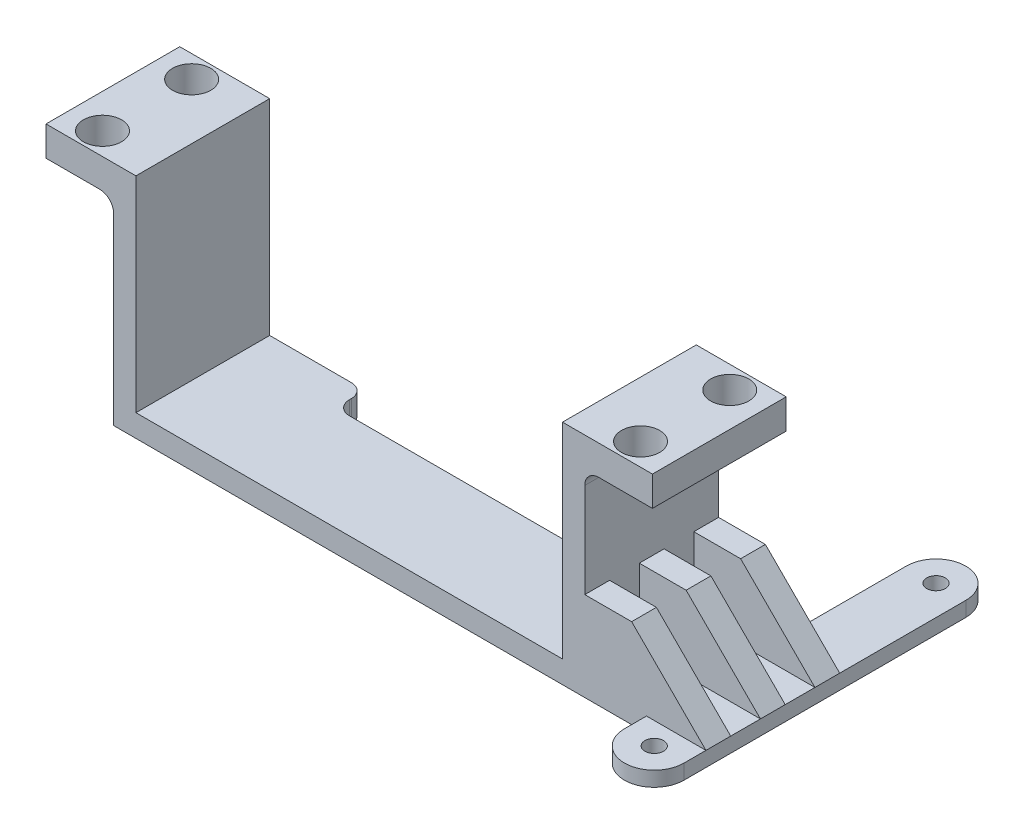
SolidWorks part; units mm, degrees
ref_plane "Front Plane" through (0, 0, 0) normal (0, 0, 1) x (1, 0, 0)
ref_plane "Top Plane" through (0, 0, 0) normal (0, 1, 0) x (1, 0, 0)
ref_plane "Right Plane" through (0, 0, 0) normal (1, 0, 0) x (0, 0, -1)
sketch "Sketch1" plane through (0, 0, 0) normal (0, 0, 1) x (1, 0, 0)
  line L0 (-3.81, 35.052) -> (0, 35.052)
  line L1 (0, 0) -> (72.898, 0)
  line L2 (0, 0) -> (0, 35.052)
  line L4 (72.898, 0) -> (72.898, 35.052)
  line L6 (-3.81, 35.052) -> (-3.81, -3.81)
  line L7 (-3.81, -3.81) -> (76.708, -3.81)
  line L8 (76.708, 35.052) -> (76.708, -3.81)
  line L9 (72.898, 35.052) -> (76.708, 35.052)
  dimension "D1" = 3.81
  dimension "D2" = 3.81
  dimension "D3" = 3.81
  dimension "D4" = 38.862
  dimension "D5" = 72.898
extrude "Boss-Extrude1" add sketch "Sketch1" along normal blind 22.86
sketch "Sketch2" plane through (0, -3.81, 0) normal (0, -1, 0) x (1, 0, 0)
  line L0 (92.329, 26.6192) -> (92.329, -21.5392) construction
  line L2 (87.249, 26.6192) -> (87.249, 22.86)
  line L3 (97.409, 26.6192) -> (97.409, -21.5392)
  line L4 (-3.81, 22.86) -> (76.708, 22.86) construction
  line L5 (76.708, 22.86) -> (76.708, 0) construction
  line L6 (76.708, 22.86) -> (87.249, 22.86)
  line L7 (76.708, 22.86) -> (76.708, 0)
  line L8 (76.708, 0) -> (87.249, 0)
  line L9 (87.249, 0) -> (87.249, -21.5392)
  circle A0 centre (92.329, 26.6192) radius 1.5875
  circle A1 centre (92.329, -21.5392) radius 1.5875
  arc A2 (97.409, 26.6192) -> (87.249, 26.6192) centre (92.329, 26.6192) ccw
  arc A3 (87.249, -21.5392) -> (97.409, -21.5392) centre (92.329, -21.5392) ccw
  point P4 (92.329, 2.54)
  point P5 (76.708, 11.43)
  point P6 (36.449, 22.86)
  point P9 (92.329, 25.0317)
  point P14 (92.329, -19.9517)
  dimension "D2" = 3.175
  dimension "D3" = 5.08
  dimension "D1" = 44.9834
  dimension "D4" = 55.88
  dimension "D5" = 8.89
extrude "Boss-Extrude2" add sketch "Sketch2" against normal blind 2.54
sketch "Sketch4" plane through (0, 35.052, 0) normal (0, 1, 0) x (1, 0, 0)
  line L0 (0, -22.86) -> (-3.81, -22.86) construction
  line L1 (0, 0) -> (-15.367, 0)
  line L2 (0, 0) -> (0, -22.86)
  line L3 (0, -22.86) -> (-15.367, -22.86)
  line L4 (-15.367, 0) -> (-15.367, -22.86)
  line L5 (-3.81, -22.86) -> (-3.81, 0) construction
  line L6 (-9.525, -3.81) -> (-9.525, -19.05) construction
  circle A0 centre (-9.525, -3.81) radius 3.2639
  circle A1 centre (-9.525, -19.05) radius 3.2639
  point P13 (-15.367, -11.43)
  point P14 (-9.525, -11.43)
  dimension "D1" = 6.5278
  dimension "D2" = 5.715
  dimension "D3" = 7.62
  dimension "D4" = 5.842
extrude "Boss-Extrude3" add sketch "Sketch4" against normal blind 5.08
ref_plane "Plane1" through (36.449, 0, 0) normal (1, 0, 0) x (0, 0, -1)
mirror "Mirror1" about plane through (36.449, 0, 0) normal (1, 0, 0) of "Boss-Extrude3"
sketch "Sketch5" plane through (0, -1.27, 0) normal (0, 1, 0) x (1, 0, 0)
  line L0 (97.409, 21.5392) -> (97.409, -26.6192) construction
  line L1 (76.708, 0) -> (97.409, 0)
  line L2 (76.708, 0) -> (76.708, -4.2333)
  line L3 (76.708, -4.2333) -> (97.409, -4.2333)
  line L4 (97.409, 0) -> (97.409, -4.2333)
  line L5 (76.708, -22.86) -> (76.708, 0) construction
  line L6 (76.708, -22.86) -> (97.409, -22.86)
  line L7 (76.708, -22.86) -> (76.708, -18.6267)
  line L8 (76.708, -18.6267) -> (97.409, -18.6267)
  line L9 (97.409, -22.86) -> (97.409, -18.6267)
  line L10 (76.708, -9.3133) -> (97.409, -9.3133)
  line L11 (76.708, -9.3133) -> (76.708, -13.5467)
  line L12 (76.708, -13.5467) -> (97.409, -13.5467)
  line L13 (97.409, -9.3133) -> (97.409, -13.5467)
  dimension "D1" = 5.08
  dimension "D2" = 5.08
extrude "Boss-Extrude4" add sketch "Sketch5" along normal blind 12.7
chamfer "Chamfer1" distance 12.7 angle 45 3 edges at (97.409, 11.43, 20.7433) (97.409, 11.43, 11.43) (97.409, 11.43, 2.1167)
fillet "Fillet1" radius 2.38 2 edges at (76.708, 29.972, 11.43) (-3.81, 29.972, 11.43)
sketch "Sketch6" plane through (0, -3.81, 0) normal (0, -1, 0) x (1, 0, 0)
  line L23 (-3.81, 0) -> (87.249, 0) construction
  line L24 (67.1195, 0) -> (16.3195, 0)
  line L25 (67.1195, 0) -> (67.1195, 5.08)
  line L26 (67.1195, 5.08) -> (16.3195, 5.08)
  line L27 (16.3195, 0) -> (16.3195, 5.08)
  point P16 (41.7195, 5.08)
  dimension "D1" = 5.08
extrude "Cut-Extrude1" cut sketch "Sketch6" against normal through all
fillet "Fillet2" radius 2.38 4 edges at (67.1195, -1.905, 0) (67.1195, -1.905, 5.08) (16.3195, -1.905, 0) (16.3195, -1.905, 5.08)
